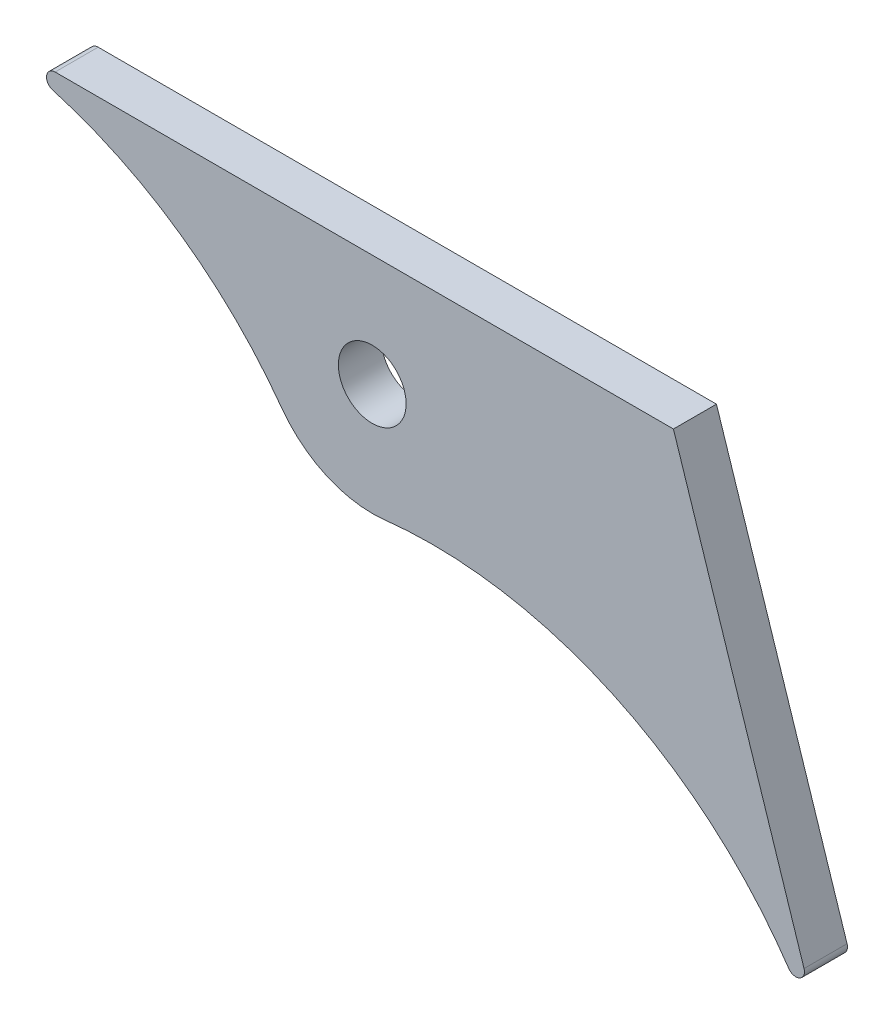
SolidWorks part; units mm, degrees
material "6061 Alloy"
ref_plane "Front Plane" through (0, 0, 0) normal (0, 0, 1) x (1, 0, 0)
ref_plane "Top Plane" through (0, 0, 0) normal (0, 1, 0) x (1, 0, 0)
ref_plane "Right Plane" through (0, 0, 0) normal (1, 0, 0) x (0, 0, -1)
sketch "Sketch1" plane through (0, 0, 0) normal (0, 0, 1) x (1, 0, 0)
  line L0 (0, 0) -> (-44.45, 0)
  line L1 (0, 0) -> (24.8248, -76.4028)
  line L2 (-44.45, 0) -> (-109.2075, 0)
  circle A0 centre (-44.45, -16.51) radius 5
  arc A1 (-57.8127, -26.2063) -> (-42.6171, -32.9179) centre (-44.45, -16.51) ccw
  arc A2 (24.8248, -76.4028) -> (-42.6171, -32.9179) centre (-35.5673, -96.0254) ccw
  arc A3 (-57.8127, -26.2063) -> (-109.2075, 0) centre (-109.2075, -63.5) ccw
  point P4 (-88.2702, 0)
  point P9 (-56.1734, -28.1351)
  point P13 (-44.45, 0)
  point P14 (-55.4452, -28.8261)
  point P15 (35.1551, -60.8903)
  dimension "D2" = 10
  dimension "D5" = 63.5
  dimension "D6" = 63.5
  dimension "D1" = 108
  dimension "D3" = 16.51
  dimension "D4" = 44.45
extrude "Boss-Extrude1" add sketch "Sketch1" along normal blind 6.35
fillet "Fillet1" radius 1.27 2 edges at (24.8248, -76.4028, 3.175) (-109.2075, 0, 3.175)
